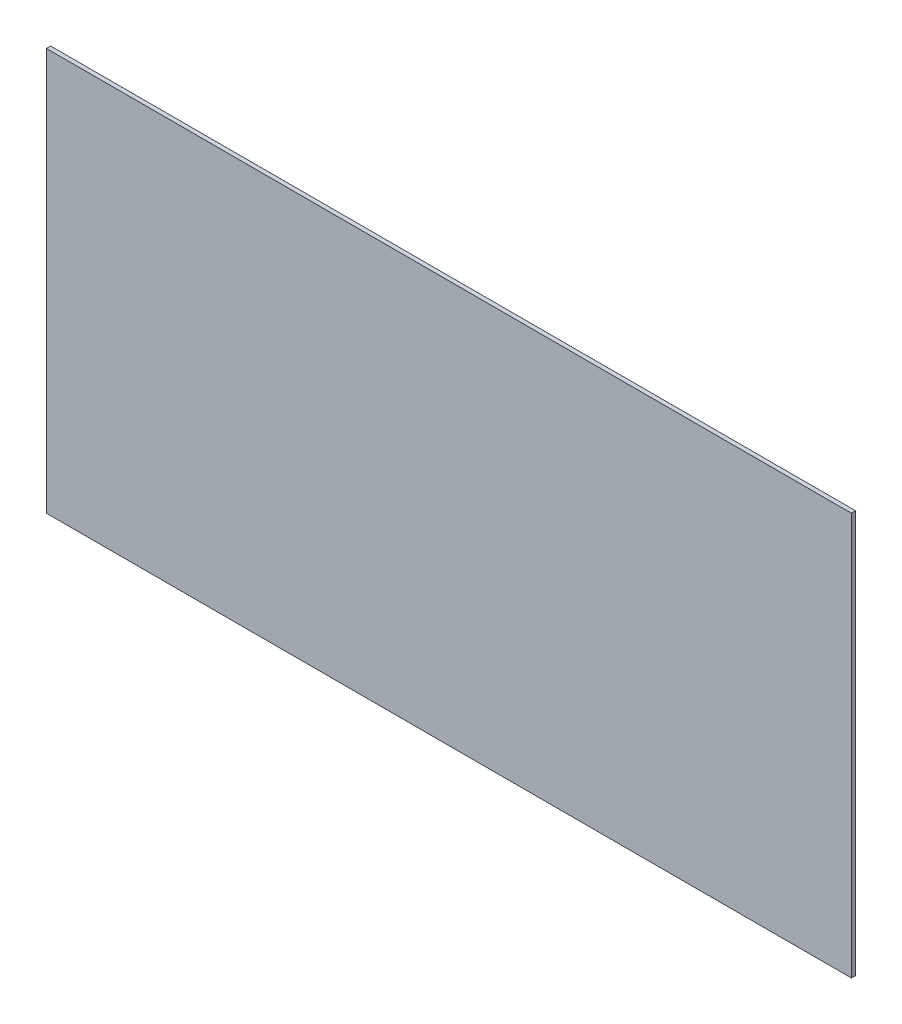
SolidWorks part; units mm, degrees
ref_plane "Front Plane" through (0, 0, 0) normal (0, 0, 1) x (1, 0, 0)
ref_plane "Top Plane" through (0, 0, 0) normal (0, 1, 0) x (1, 0, 0)
ref_plane "Right Plane" through (0, 0, 0) normal (1, 0, 0) x (0, 0, -1)
sketch "Sketch1" plane through (0, 0, 0) normal (0, 0, 1) x (1, 0, 0)
  line L1 (-238.8538, 271.0227) -> (370.7462, 271.0227)
  line L2 (-238.8538, 271.0227) -> (-238.8538, -33.7773)
  line L3 (-238.8538, -33.7773) -> (370.7462, -33.7773)
  line L4 (370.7462, 271.0227) -> (370.7462, -33.7773)
  dimension "D1" = 609.6
  dimension "D2" = 304.8
extrude "Boss-Extrude1" add sketch "Sketch1" along normal blind 3.175
